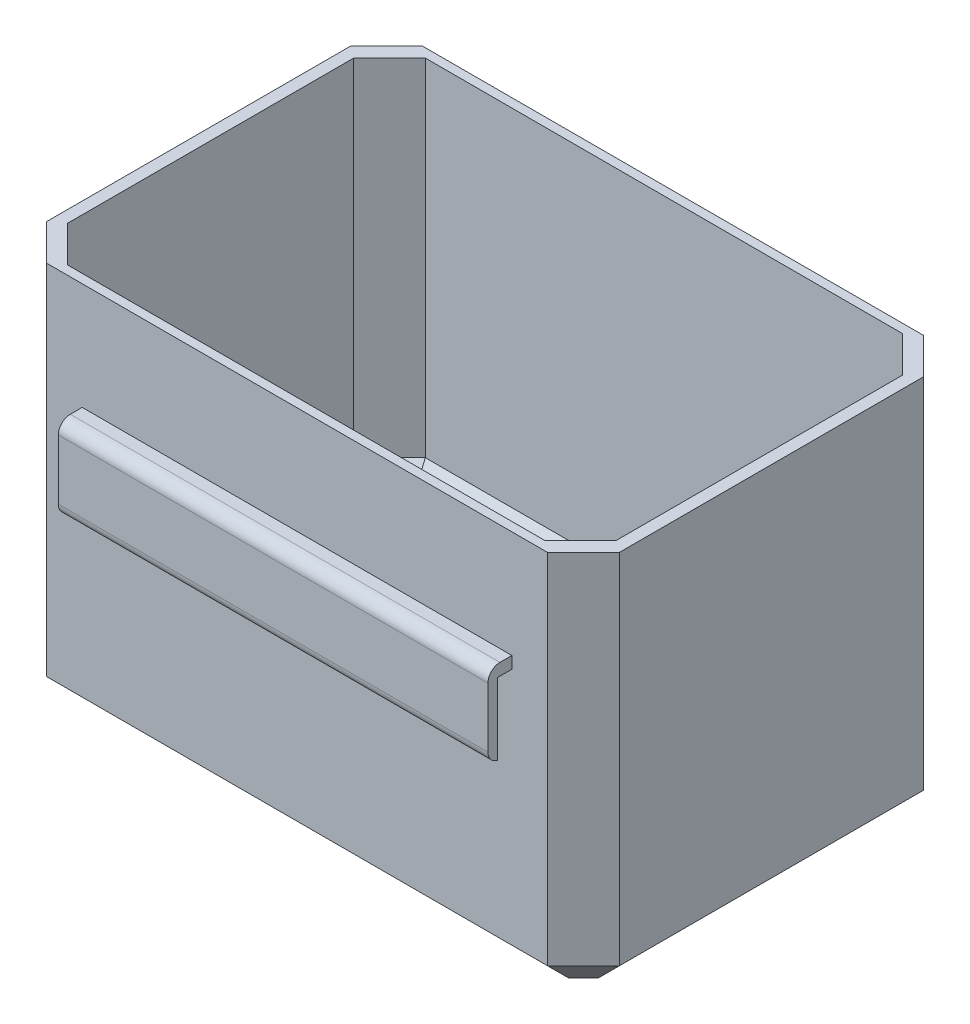
SolidWorks part; units mm, degrees
ref_plane "Front Plane" through (0, 0, 0) normal (0, 0, 1) x (1, 0, 0)
ref_plane "Top Plane" through (0, 0, 0) normal (0, 1, 0) x (1, 0, 0)
ref_plane "Right Plane" through (0, 0, 0) normal (1, 0, 0) x (0, 0, -1)
sketch "Sketch1" plane through (0, 0, 0) normal (0, 1, 0) x (1, 0, 0)
  line L1 (240, 157.5) -> (-240, 157.5)
  line L2 (240, 157.5) -> (240, -157.5)
  line L3 (240, -157.5) -> (-240, -157.5)
  line L4 (-240, 157.5) -> (-240, -157.5)
  line L5 (240, 157.5) -> (-240, -157.5) construction
  line L6 (240, -157.5) -> (-240, 157.5) construction
  point P0 (0, 0)
  dimension "D1" = 315
  dimension "D2" = 480
extrude "Boss-Extrude1" add sketch "Sketch1" along normal blind 330
sketch "Sketch9" plane through (0, 330, 0) normal (0, 1, 0) x (1, 0, 0)
  line L1 (-230, 150) -> (230, 150)
  line L2 (-230, 150) -> (-230, -150)
  line L3 (-230, -150) -> (230, -150)
  line L4 (230, 150) -> (230, -150)
  line L5 (-230, 150) -> (230, -150) construction
  line L6 (-230, -150) -> (230, 150) construction
  point P0 (0, 0)
  dimension "D1" = 300
  dimension "D2" = 460
extrude "Cut-Extrude1" cut sketch "Sketch9" against normal blind 320
chamfer "Chamfer1" distance 30 angle 45 8 edges at (240, 165, -157.5) (-240, 165, -157.5) (-240, 165, 157.5) (240, 165, 157.5) (230, 170, 150) (-230, 170, 150) (-230, 170, -150) (230, 170, -150)
chamfer "Chamfer2" distance 30 angle 45 16 edges at (-240, 0, 0) (-225, 0, -142.5) (0, 0, -157.5) (225, 0, -142.5) (240, 0, 0) (225, 0, 142.5) (-225, 0, 142.5) (0, 0, 157.5) (215, 10, -135) (230, 10, 0) (215, 10, 135) (0, 10, 150) (-215, 10, 135) (-230, 10, 0) (-215, 10, -135) (0, 10, -150)
sketch "Sketch11" plane through (0, 0, 157.5) normal (0, 0, 1) x (1, 0, 0)
  line L0 (0, 0) -> (0, 462.9068) construction
  line L2 (-180, 230.2511) -> (180, 230.2511)
  line L3 (-180, 230.2511) -> (-180, 240.2511)
  line L4 (-180, 240.2511) -> (180, 240.2511)
  line L5 (180, 230.2511) -> (180, 240.2511)
  line L6 (-180, 230.2511) -> (180, 240.2511) construction
  line L7 (-180, 240.2511) -> (180, 230.2511) construction
  point P3 (0, 235.2511)
  dimension "D1" = 10
  dimension "D2" = 360
extrude "Boss-Extrude2" add sketch "Sketch11" along normal blind 20
sketch "Sketch12" plane through (0, 230.2511, 0) normal (0, -1, 0) x (1, 0, 0)
  line L0 (180, 177.5) -> (180, 157.5) construction
  line L1 (-180, 177.5) -> (180, 177.5)
  line L2 (-180, 177.5) -> (-180, 169.5)
  line L3 (-180, 169.5) -> (180, 169.5)
  line L4 (180, 177.5) -> (180, 169.5)
  dimension "D1" = 8
extrude "Boss-Extrude3" add sketch "Sketch12" along normal blind 60
fillet "Fillet1" radius 10 2 edges at (0, 170.2511, 177.5) (0, 240.2511, 177.5)
